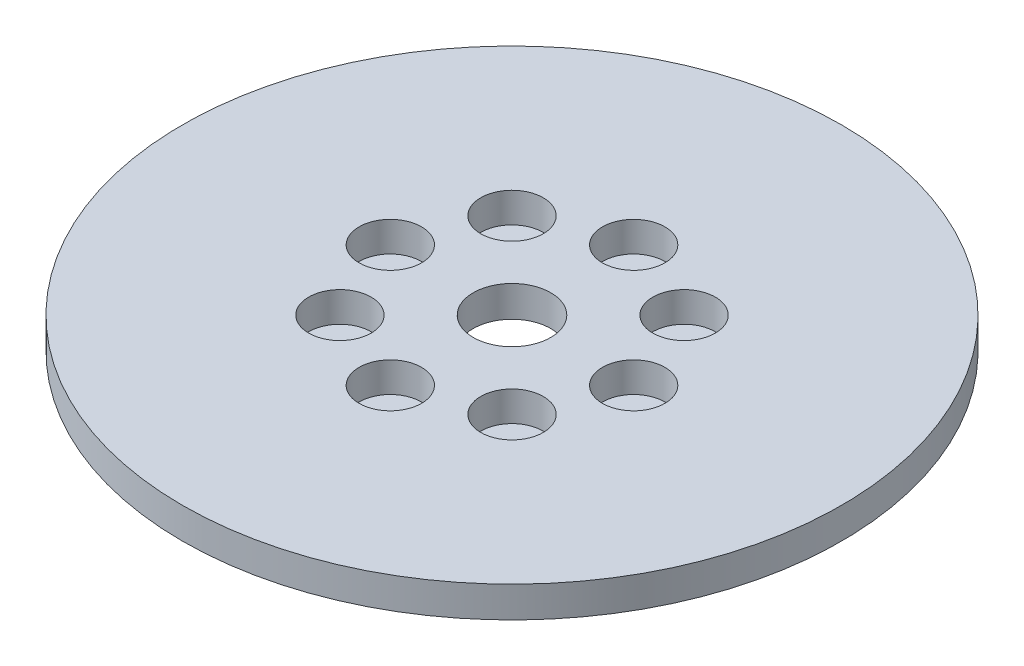
SolidWorks part; units mm, degrees
ref_plane "Front Plane" through (0, 0, 0) normal (0, 0, 1) x (1, 0, 0)
ref_plane "Top Plane" through (0, 0, 0) normal (0, 1, 0) x (1, 0, 0)
ref_plane "Right Plane" through (0, 0, 0) normal (1, 0, 0) x (0, 0, -1)
sketch "Sketch1" plane through (0, 0, 0) normal (0, 1, 0) x (1, 0, 0)
  circle A0 centre (0, 0) radius 42.5
  dimension "FLANGE_OD" = 85
extrude "Boss-Extrude1" add sketch "Sketch1" along normal blind 4
sketch "Sketch2" plane through (0, 0, 0) normal (0, 1, 0) x (1, 0, 0)
  circle A0 centre (0, 0) radius 5
  dimension "BORE_D" = 10
extrude "Cut-Extrude1" cut sketch "Sketch2" along normal through all
sketch "Sketch3" plane through (0, 4, 0) normal (0, 1, 0) x (1, 0, 0)
  circle A0 centre (0, 0) radius 15.6918 construction
  circle A1 centre (-15.6918, 0) radius 4.0288
  dimension "BOLT_D" = 8.0577
  dimension "BOLT_PCD" = 31.3835
extrude "Cut-Extrude2" cut sketch "Sketch3" against normal blind 3.8722
pattern_circular "CirPattern1" count 8 over 360 about axis through (0, 0, 0) along (0, 1, 0) of "Cut-Extrude2"
